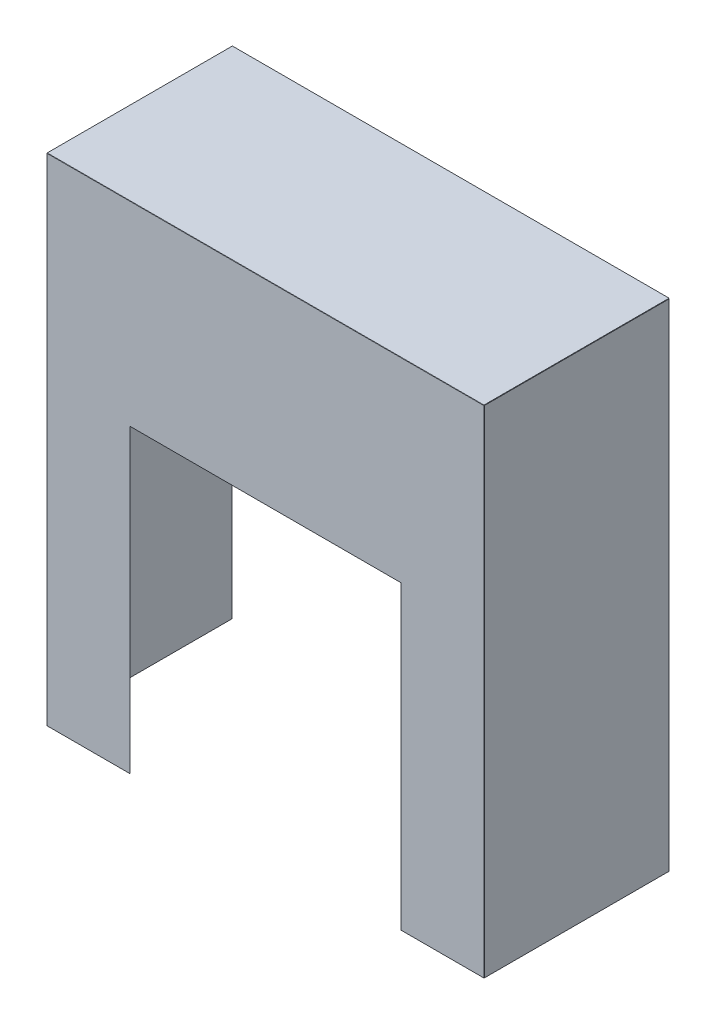
SolidWorks part; units mm, degrees
note: The reader was unsure of these and kept them because the rebuilt part matched: flange length of "Edge-Flange1", "Edge-Flange2", "Edge-Flange3".
ref_plane "Front Plane" through (0, 0, 0) normal (0, 0, 1) x (1, 0, 0)
ref_plane "Top Plane" through (0, 0, 0) normal (0, 1, 0) x (1, 0, 0)
ref_plane "Right Plane" through (0, 0, 0) normal (1, 0, 0) x (0, 0, -1)
sketch "Sketch1" plane through (0, 0, 0) normal (0, 1, 0) x (1, 0, 0)
  line L1 (0, 0) -> (-2950, 0)
  line L2 (0, 0) -> (0, 1250)
  line L3 (0, 1250) -> (-2950, 1250)
  line L4 (-2950, 0) -> (-2950, 1250)
  dimension "D1" = 2950
  dimension "D2" = 1250
base flange "Base-Flange1" sketch "Sketch1" thickness 1.27 reverse thickness direction no parameters "D1"=0.7366
edge flange "Edge-Flange1" sketch "Sketch9" flange angle 90 flange length 3350 flange position bend outside bend radius 0.7366 thickness 1.27 relief rectangular parameters "D6"=10
sketch "Sketch9" plane through (0, -1.27, 0) normal (0, 0, -1) x (1, 0, 0)
  line L2 (-2950, 0) -> (-2950, 3348.73)
  line L3 (-2950, 3348.73) -> (0, 3348.73)
  line L4 (0, 3348.73) -> (0, 0)
  line L5 (0, 0) -> (-2950, 0) construction
  line L6 (0, 0) -> (-2950, 0)
bend "EdgeBend1" bend radius 0.7366 bend angle 90 parameters "D5"=1
edge flange "Edge-Flange2" sketch "Sketch20" flange angle 90 flange length 1250 flange position bend outside bend radius 0.7366 thickness 1.27 relief rectangular parameters "D6"=10
bend "EdgeBend4" bend radius 0.7366 bend angle 90 parameters "D5"=2
sketch "Sketch20" plane through (0, 0, 0.7366) normal (-1, 0, 0) x (0, 1, 0)
  line L0 (-2.0066, 0) -> (-3350, 0) construction
  line L1 (-2.0066, 0) -> (-3350, 0)
  line L2 (-2.0066, 0) -> (-2.0066, 1248.73)
  line L3 (-2.0066, 1248.73) -> (-3350, 1248.73)
  line L4 (-3350, 1248.73) -> (-3350, 0)
edge flange "Edge-Flange3" sketch "Sketch22" flange angle 90 flange length 1250 flange position bend outside bend radius 0.7366 thickness 1.27 relief rectangular parameters "D6"=10
bend "EdgeBend5" bend radius 0.7366 bend angle 90 parameters "D5"=3
sketch "Sketch22" plane through (-2950, 0, 0.7366) normal (1, 0, 0) x (0, -1, 0)
  line L0 (3350, 0) -> (2.0066, 0) construction
  line L1 (3350, 0) -> (2.0066, 0)
  line L2 (3350, 0) -> (3350, 1248.73)
  line L3 (3350, 1248.73) -> (2.0066, 1248.73)
  line L4 (2.0066, 1248.73) -> (2.0066, 0)
sketch "Sketch16" plane through (0, 0, 2.0066) normal (0, 0, 1) x (1, 0, 0)
  line L1 (-560.6, -3350) -> (-2389.4, -3350)
  line L2 (-560.6, -3350) -> (-560.6, -1318)
  line L3 (-560.6, -1318) -> (-2389.4, -1318)
  line L4 (-2389.4, -3350) -> (-2389.4, -1318)
  point P5 (-1215.5757, -3350)
  dimension "D1" = 1828.8
  dimension "D2" = 2032
extrude "Cut-Extrude1" cut sketch "Sketch16" against normal up to next normal cut yes
sketch "Sketch17" plane through (0, 0, 2.0066) normal (0, 0, 1) x (1, 0, 0)
  line L1 (-2389.4, -1318) -> (-560.6, -1318)
  line L2 (-2389.4, -1318) -> (-2389.4, -3350)
  line L3 (-2389.4, -3350) -> (-560.6, -3350)
  line L4 (-560.6, -1318) -> (-560.6, -3350)
sketch "Bend-Lines1" [suppressed] plane through (0, 0, 0) normal (0, 1, 0) x (1, 0, 0)
sketch "Bounding-Box1" [suppressed] plane through (0, 0, 0) normal (0, 1, 0) x (1, 0, 0)
sheet metal parameters "Sheet-Metal1" thickness 1.27 parameters "D1"=0.7366
flat pattern "Flat-Pattern1" [suppressed]
sketch "Bend-Lines2" plane through (0, 0, 0) normal (0, 1, 0) x (1, 0, 0)
sketch3d "Bounding-Box2" [suppressed]
  line L0 (0, 0, 0) -> (2900, 0, 0) construction
  line L1 (0, 1250, 0) -> (2900, 1250, 0) construction
  line L2 (0, 0, 0) -> (0, 1250, 0) construction
  line L3 (2900, 0, 0) -> (2900, 1250, 0) construction
sheet metal parameters "Sheet-Metal2" thickness 1.27 parameters "D1"=0.7366
flat pattern "Flat-Pattern1"
sketch "Bend-Lines2" plane through (0, 0, 0) normal (0, 1, 0) x (1, 0, 0)
  line L0 (-2900, -1.0773) -> (0, -1.0773) construction
  line L1 (-2900, -1.0773) -> (0, -1.0773) construction
sketch3d "Bounding-Box2" [suppressed]
  line L0 (-2900, 1250, 0) -> (-2900, -3300.1479, 0) construction
  line L1 (0, 1250, 0) -> (0, -3300.1479, 0) construction
  line L2 (-2900, 1250, 0) -> (0, 1250, 0) construction
  line L3 (-2900, -3300.1479, 0) -> (0, -3300.1479, 0) construction
bend of the flat pattern "Flatten-<EdgeBend1>1"
sheet metal parameters "Sheet-Metal3" thickness 1.27 parameters "D1"=0.7366
flat pattern "Flat-Pattern1" [suppressed]
sketch "Bend-Lines2" plane through (0, 0, 0) normal (0, 1, 0) x (1, 0, 0)
  line L0 (-2900, -1.0773) -> (0, -1.0773) construction
  line L1 (-2900, -1.0773) -> (0, -1.0773) construction
  line L2 (1.0773, 0) -> (1.0773, 1250) construction
  line L3 (1.0773, 0) -> (1.0773, 1250) construction
sketch3d "Bounding-Box2" [suppressed]
  line L0 (3300.1479, -3300.1479, 0) -> (-2900, -3300.1479, 0) construction
  line L1 (3300.1479, 1250, 0) -> (-2900, 1250, 0) construction
  line L2 (3300.1479, -3300.1479, 0) -> (3300.1479, 1250, 0) construction
  line L3 (-2900, -3300.1479, 0) -> (-2900, 1250, 0) construction
bend of the flat pattern "Flatten-<EdgeBend1>1"
bend of the flat pattern "Flatten-<EdgeBend4>1"
sheet metal parameters "Sheet-Metal4" thickness 1.27 parameters "D1"=0.7366
flat pattern "Flat-Pattern1" [suppressed]
sketch "Bend-Lines2" plane through (0, 0, 0) normal (0, 1, 0) x (1, 0, 0)
  line L0 (-2950, -1.0773) -> (0, -1.0773) construction
  line L1 (-2950, -1.0773) -> (0, -1.0773) construction
  line L2 (1.0773, 0) -> (1.0773, 1250) construction
  line L3 (1.0773, 0) -> (1.0773, 1250) construction
  line L4 (-2951.0773, 1250) -> (-2951.0773, 0) construction
  line L5 (-2951.0773, 1250) -> (-2951.0773, 0) construction
sketch3d "Bounding-Box2" [suppressed]
  line L0 (3350.1479, -3350.1479, 0) -> (-6300.1479, -3350.1479, 0) construction
  line L1 (3350.1479, 1250, 0) -> (-6300.1479, 1250, 0) construction
  line L2 (3350.1479, -3350.1479, 0) -> (3350.1479, 1250, 0) construction
  line L3 (-6300.1479, -3350.1479, 0) -> (-6300.1479, 1250, 0) construction
bend of the flat pattern "Flatten-<EdgeBend1>1"
bend of the flat pattern "Flatten-<EdgeBend4>2"
bend of the flat pattern "Flatten-<EdgeBend5>1"
sheet metal parameters "Sheet-Metal5" thickness 1.27 parameters "D1"=0.7366
flat pattern "Flat-Pattern1" [suppressed]
sketch "Bend-Lines2" plane through (0, 0, 0) normal (0, 1, 0) x (1, 0, 0)
  line L0 (-2950, -1.0773) -> (0, -1.0773) construction
  line L1 (-2950, -1.0773) -> (0, -1.0773) construction
  line L2 (-2951.0773, -2.1545) -> (-2951.0773, -3350.1479) construction
  line L3 (-2951.0773, -2.1545) -> (-2951.0773, -3350.1479) construction
  line L6 (1.0773, -3350.1479) -> (1.0773, -2.1545) construction
  line L7 (1.0773, -3350.1479) -> (1.0773, -2.1545) construction
sketch3d "Bounding-Box2" [suppressed]
  line L0 (1250.1479, -3350.1479, 0) -> (-4200.1479, -3350.1479, 0) construction
  line L1 (1250.1479, 1250, 0) -> (-4200.1479, 1250, 0) construction
  line L2 (1250.1479, -3350.1479, 0) -> (1250.1479, 1250, 0) construction
  line L3 (-4200.1479, -3350.1479, 0) -> (-4200.1479, 1250, 0) construction
bend of the flat pattern "Flatten-<EdgeBend1>1"
bend of the flat pattern "Flatten-<EdgeBend4>3"
bend of the flat pattern "Flatten-<EdgeBend5>2"
sketch "Sketch17-1" [suppressed] plane through (0, 0, 0.1479) normal (0, 1, 0) x (1, 0, 0)
  line L1 (-2389.4, -1318) -> (-560.6, -1318)
  line L2 (-2389.4, -1318) -> (-2389.4, -3350)
  line L3 (-2389.4, -3350) -> (-560.6, -3350)
  line L4 (-560.6, -1318) -> (-560.6, -3350)
